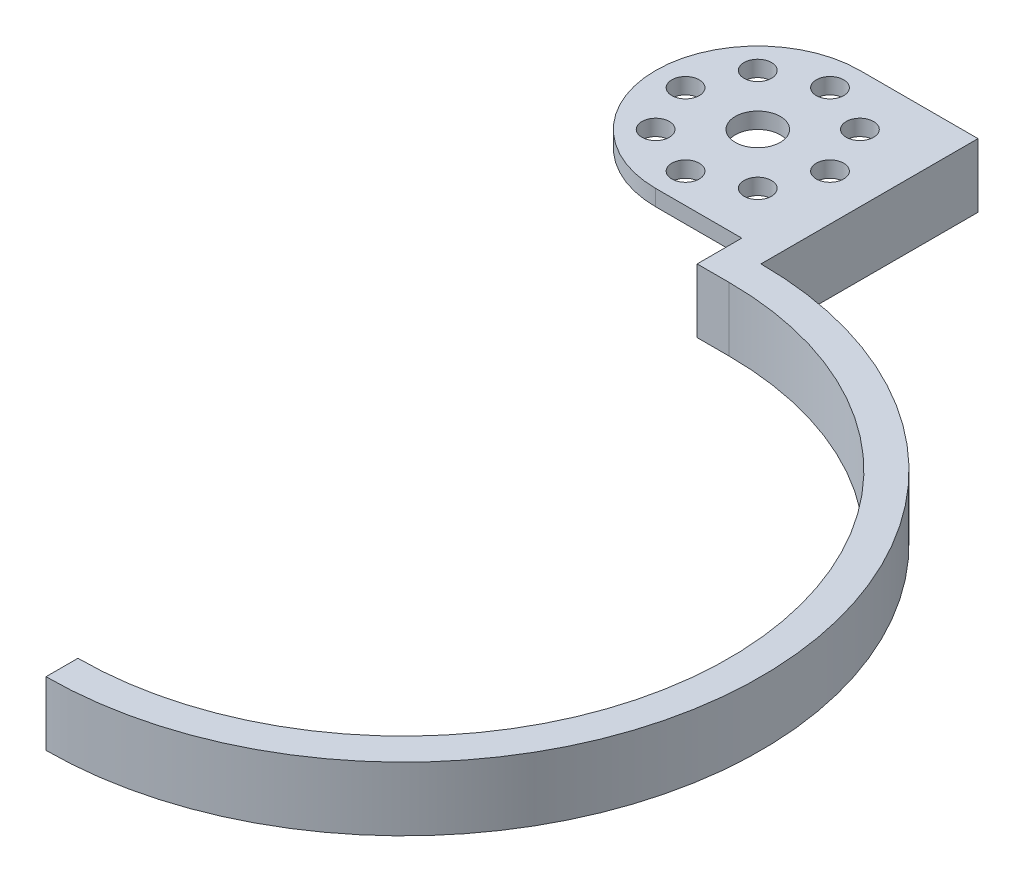
SolidWorks part; units mm, degrees
ref_plane "Front Plane" through (0, 0, 0) normal (0, 0, 1) x (1, 0, 0)
ref_plane "Top Plane" through (0, 0, 0) normal (0, 1, 0) x (1, 0, 0)
ref_plane "Right Plane" through (0, 0, 0) normal (1, 0, 0) x (0, 0, -1)
sketch "Sketch4" plane through (0, 0, 0) normal (0, 1, 0) x (1, 0, 0)
  line L1 (1.7601, -30.9271) -> (20.2601, -30.9271)
  line L2 (1.7601, -30.9271) -> (1.7601, -62.9271)
  line L3 (1.7601, -62.9271) -> (20.2601, -62.9271)
  line L4 (20.2601, -30.9271) -> (20.2601, -62.9271)
  dimension "D1" = 32
  dimension "D2" = 18.5
extrude "Boss-Extrude2" add sketch "Sketch4" along normal blind 2.5
sketch "Sketch5" plane through (0, 0, 0) normal (0, 1, 0) x (1, 0, 0)
  line L0 (1.7601, -30.9271) -> (1.7601, -62.9271) construction
  circle A0 centre (1.7601, -46.9271) radius 16
extrude "Boss-Extrude3" add sketch "Sketch5" along normal blind 2.5
sketch "Sketch6" plane through (0, 0, 0) normal (0, 1, 0) x (1, 0, 0)
  line L0 (1.7601, -62.9271) -> (20.2601, -62.9271) construction
  line L1 (20.2601, -62.9271) -> (15.2601, -62.9271)
  line L2 (20.2601, -62.9271) -> (20.2601, -69.9271)
  line L3 (20.2601, -69.9271) -> (15.2601, -69.9271)
  line L4 (15.2601, -62.9271) -> (15.2601, -69.9271)
  line L5 (20.2601, -62.9271) -> (20.2601, -30.9271) construction
  dimension "D1" = 5
  dimension "D2" = 7
extrude "Boss-Extrude4" add sketch "Sketch6" along normal blind 2.5 and the other way blind 7.5 contours L2 L3 L4 L1
sketch "Sketch9" plane through (0, 0, 0) normal (0, 1, 0) x (1, 0, 0)
  line L2 (-6.2399, -38.9271) -> (9.7601, -38.9271) construction
  line L3 (-6.2399, -38.9271) -> (-6.2399, -54.9271) construction
  line L4 (-6.2399, -54.9271) -> (9.7601, -54.9271) construction
  line L5 (9.7601, -38.9271) -> (9.7601, -54.9271) construction
  line L6 (-6.2399, -38.9271) -> (9.7601, -54.9271) construction
  line L7 (-6.2399, -54.9271) -> (9.7601, -38.9271) construction
  circle A0 centre (1.7601, -46.9271) radius 16
  circle A2 centre (1.7601, -35.6133) radius 2.15
  circle A3 centre (9.7601, -38.9271) radius 2.15
  circle A4 centre (13.0738, -46.9271) radius 2.15
  circle A5 centre (9.7601, -54.9271) radius 2.15
  circle A6 centre (1.7601, -58.2408) radius 2.15
  circle A7 centre (-6.2399, -54.9271) radius 2.15
  circle A8 centre (-9.5536, -46.9271) radius 2.15
  circle A9 centre (-6.2399, -38.9271) radius 2.15
  circle A10 centre (1.7601, -46.9271) radius 3.525
  dimension "D2" = 32
  dimension "D3" = 4.3
  dimension "D5" = 7.05
  dimension "D4" = 8
extrude "Cut-Extrude1" cut sketch "Sketch9" along normal blind 2.5 contours A6 | A5 | A4 | A3 | A2 | A8 | A7 | A9
extrude "Cut-Extrude3" cut sketch "Sketch9<3>" along normal blind 2.5 contours A10
sketch "Sketch9<3>" plane through (0, 0, 0) normal (0, 1, 0) x (1, 0, 0) same geometry as "Sketch9"
sketch "Sketch14" plane through (0, -7.5, 0) normal (0, -1, 0) x (-1, 0, 0)
  line L2 (-20.2601, -171.9271) -> (-20.2601, -176.9271)
  line L3 (-20.2601, -69.9271) -> (-20.2601, -64.9271)
  arc A0 (-20.2601, -69.9271) -> (-20.2601, -171.9271) centre (-20.2601, -120.9271) ccw
  arc A1 (-20.2601, -64.9271) -> (-20.2601, -176.9271) centre (-20.2601, -120.9271) ccw
  circle A2 centre (-20.2601, -120.9271) radius 56 construction
  circle A3 centre (-20.2601, -120.9271) radius 51 construction
  dimension "D1" = 102
  dimension "D2" = 5
extrude "Boss-Extrude7" add sketch "Sketch14" against normal blind 10
sketch "Sketch16" plane through (0, 0, 0) normal (0, -1, 0) x (-1, 0, 0)
  line L1 (-20.2601, -30.9271) -> (-15.2601, -30.9271)
  line L2 (-20.2601, -30.9271) -> (-20.2601, -62.9271)
  line L3 (-20.2601, -62.9271) -> (-15.2601, -62.9271)
  line L4 (-15.2601, -30.9271) -> (-15.2601, -62.9271)
extrude "Boss-Extrude8" add sketch "Sketch16" along normal blind 7.5
